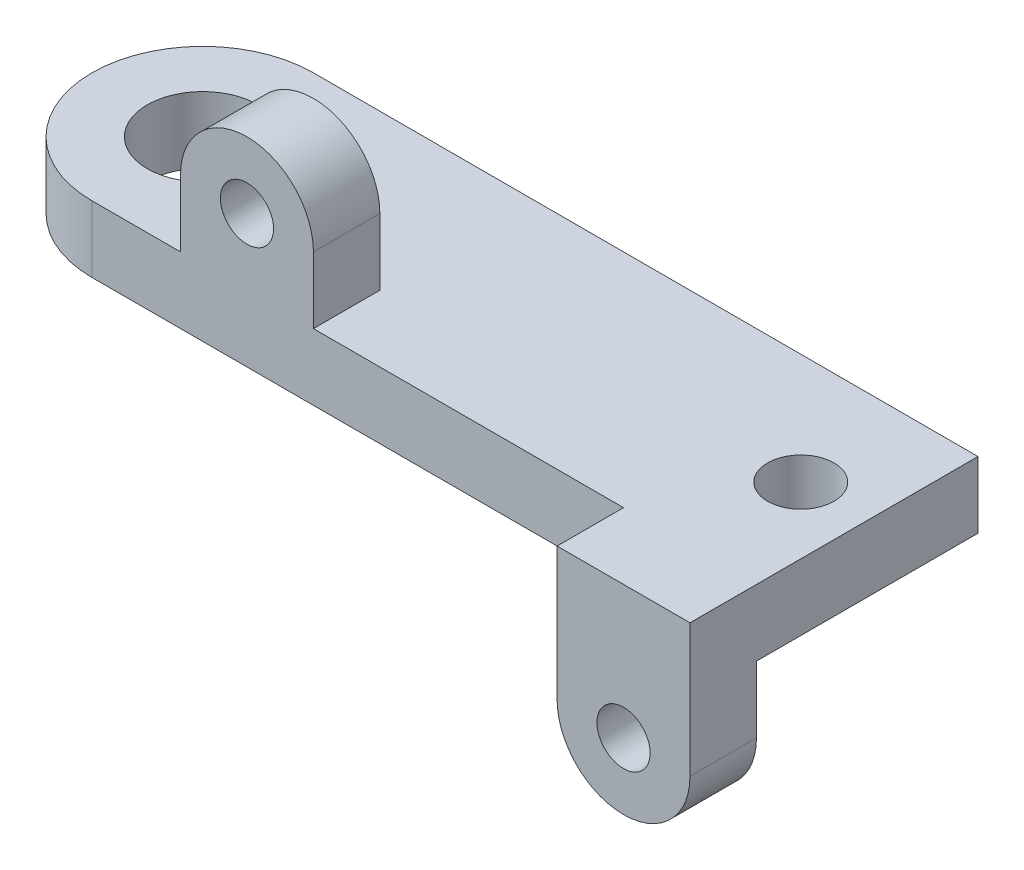
SolidWorks part; units mm, degrees
note: The reader was unsure of these and kept them because the rebuilt part matched: shared geometry of "Sketch1<3>", "Sketch1<4>".
ref_plane "Front Plane" through (0, 0, 0) normal (0, 0, 1) x (1, 0, 0)
ref_plane "Top Plane" through (0, 0, 0) normal (0, 1, 0) x (1, 0, 0)
ref_plane "Right Plane" through (0, 0, 0) normal (1, 0, 0) x (0, 0, -1)
sketch "Sketch1" plane through (0, 0, 0) normal (0, 1, 0) x (1, 0, 0)
  line L0 (0, 25) -> (150, 25)
  line L1 (150, 25) -> (150, -40)
  line L2 (150, -40) -> (120, -40)
  line L3 (120, -40) -> (120, -25)
  line L4 (0, -25) -> (120, -25)
  line L5 (20, -25) -> (20, -10)
  line L6 (20, -10) -> (50, -10)
  line L7 (50, -10) -> (50, -25)
  line L8 (120, -25) -> (150, -25)
  circle A0 centre (0, 0) radius 12.5
  arc A1 (0, 25) -> (0, -25) centre (0, 0) ccw
  circle A2 centre (135, 0) radius 7.5
  point P3 (135, -40)
  dimension "D1" = 150
  dimension "D2" = 25
  dimension "D3" = 15
  dimension "D4" = 50
  dimension "D5" = 15
  dimension "D6" = 30
  dimension "D7" = 15
  dimension "D8" = 30
  dimension "D9" = 20
extrude "Boss-Extrude1" add sketch "Sketch1" along normal blind 15 contours L0 A1 L4 L5 L6 L7 L8 L1 A2 A0
extrude "Boss-Extrude2" add sketch "Sketch1<3>" along normal blind 45 contours L7 L6 L5 L4
sketch "Sketch1<3>" plane through (0, 0, 0) normal (0, 1, 0) x (1, 0, 0) same geometry as "Sketch1"
extrude "Boss-Extrude3" add sketch "Sketch1<4>" against normal blind 45 from offset 15 contours L8 L3 L2 L1
sketch "Sketch1<4>" plane through (0, 0, 0) normal (0, 1, 0) x (1, 0, 0) same geometry as "Sketch1"
sketch "Sketch3" plane through (0, 0, 0) normal (0, 0, 1) x (1, 0, 0)
  line L0 (20, 45) -> (50, 45) construction
  line L1 (50, 45) -> (50, 15) construction
  line L2 (20, 45) -> (20, 15) construction
  line L3 (150, -30) -> (150, 15) construction
  line L4 (150, -30) -> (120, -30) construction
  line L5 (120, -30) -> (120, 15) construction
  line L6 (50, 30) -> (50, 45)
  line L7 (50, 45) -> (20, 45)
  line L8 (20, 45) -> (20, 30)
  line L9 (120, -15) -> (120, -39.4271)
  line L10 (120, -39.4271) -> (150, -39.4271)
  line L11 (150, -39.4271) -> (150, -15)
  circle A0 centre (35, 30) radius 6
  circle A1 centre (35, 30) radius 15
  circle A2 centre (135, -15) radius 6
  circle A3 centre (135, -15) radius 15
  dimension "D1" = 12
  dimension "D2" = 12
extrude "Cut-Extrude1" cut sketch "Sketch3" along normal up to next contours A1 L6 L7 | A1 L7 L8 | A0 | A3 L9 L10 L11 | A2
